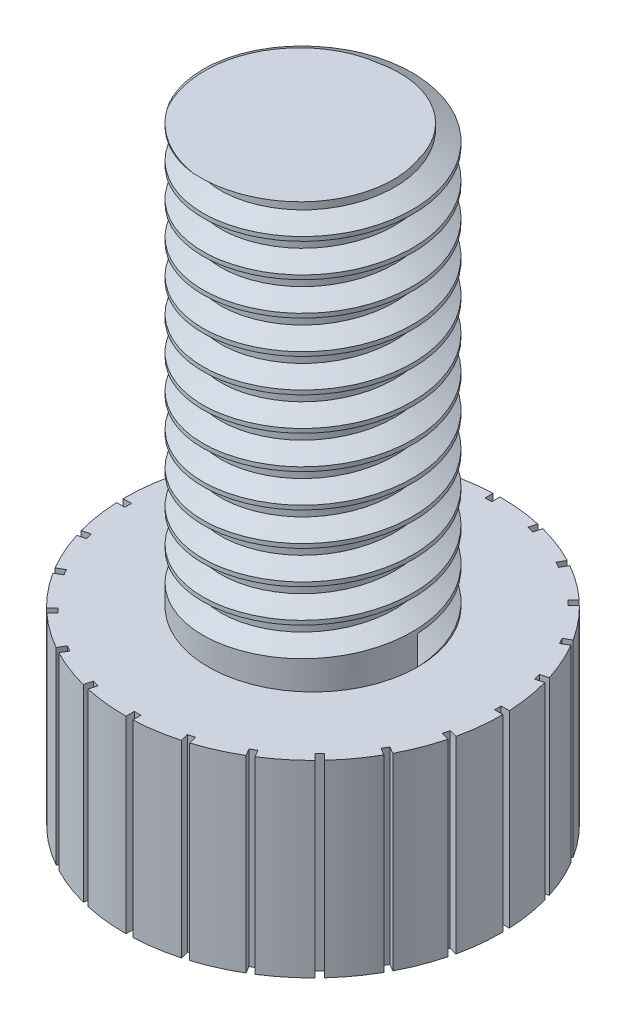
SolidWorks part; units mm, degrees
ref_plane "前视基准面" through (0, 0, 0) normal (0, 0, 1) x (1, 0, 0)
ref_plane "上视基准面" through (0, 0, 0) normal (0, 1, 0) x (1, 0, 0)
ref_plane "右视基准面" through (0, 0, 0) normal (1, 0, 0) x (0, 0, -1)
sketch "草图1" plane through (0, 0, 0) normal (0, 1, 0) x (1, 0, 0)
  circle A0 centre (0, 0) radius 1.8
  dimension "D1" = 3.6
extrude "凸台-拉伸1" add sketch "草图1" along normal blind 1.8
sketch "草图2" plane through (0, 1.8, 0) normal (0, 1, 0) x (1, 0, 0)
  circle A0 centre (0, 0) radius 1
  dimension "D1" = 2
extrude "凸台-拉伸2" add sketch "草图2" along normal blind 4
thread "螺纹线1" pitch 0.3175 method cut profile "螺纹线轮廓2" start angle 0, offset 0, length 6, pitch 0.3175, diameter 2
ref_plane "基准面2" through (1, 1.8, 0) normal (0, 0, 1) x (1, 0, 0)
sketch "螺纹线轮廓2" plane through (1, 1.8, 0) normal (0, 0, 1) x (1, 0, 0)
  line L0 (0, 0) -> (0, 0.3175) construction
  line L11 (0, 0) -> (0, 0.2778)
  line L12 (0, 0.2778) -> (-0.1719, 0.1786)
  line L13 (-0.1719, 0.1786) -> (-0.1719, 0.0992)
  line L15 (-0.1719, 0.0992) -> (0, 0)
  line L17 (-0.1719, 0.1389) -> (0, 0.1389) construction
  point P2 (0, 0)
  dimension "Pitch" = 0.3175
  dimension "Profile_Angle" = 60
  dimension "Profile_Land" = 0.0794
  dimension "Profile_Height" = 0.1719
sketch "草图7" plane through (0, 0, 0) normal (0, -1, 0) x (-1, 0, 0)
  line L1 (-0.866, 0) -> (-0.433, -0.75)
  line L2 (-0.433, -0.75) -> (0.433, -0.75)
  line L3 (0.433, -0.75) -> (0.866, 0)
  line L4 (0.866, 0) -> (0.433, 0.75)
  line L5 (0.433, 0.75) -> (-0.433, 0.75)
  line L6 (-0.433, 0.75) -> (-0.866, 0)
  circle A0 centre (0, 0) radius 0.75 construction
  dimension "D1" = 1.5
extrude "切除-拉伸1" cut sketch "草图7" against normal blind 1
sketch "草图8" plane through (0, 0, 0) normal (0, -1, 0) x (-1, 0, 0)
  line L4 (0.0138, 1.7208) -> (0.0768, 1.7208)
  line L5 (0.0138, 1.7208) -> (0.0138, 1.9428)
  line L6 (0.0138, 1.9428) -> (0.0768, 1.9428)
  line L7 (0.0768, 1.7208) -> (0.0768, 1.9428)
extrude "切除-拉伸2" cut sketch "草图8" against normal blind 2
sketch "草图10" plane through (0, 0, 0) normal (0, 0, 1) x (1, 0, 0)
  line L0 (0, -0.405) -> (0, 2.0875) construction
pattern_circular "阵列(圆周)2" count 24 over 360 about axis through (0, -0.405, 0) along (0, 1, 0) of "切除-拉伸2" reverse direction yes
